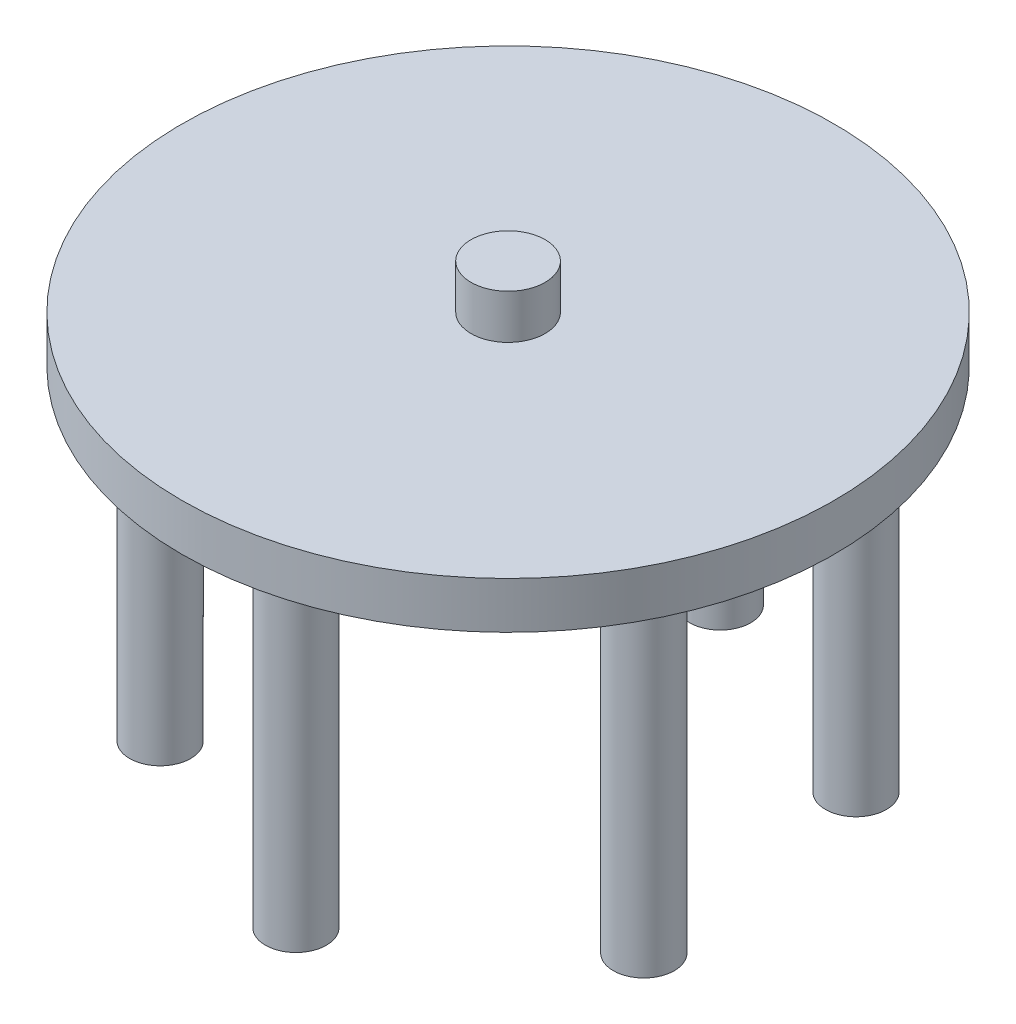
SolidWorks part; units mm, degrees
ref_plane "Front Plane" through (0, 0, 0) normal (0, 0, 1) x (1, 0, 0)
ref_plane "Top Plane" through (0, 0, 0) normal (0, 1, 0) x (1, 0, 0)
ref_plane "Right Plane" through (0, 0, 0) normal (1, 0, 0) x (0, 0, -1)
sketch "Sketch1" plane through (0, 0, 0) normal (0, 1, 0) x (1, 0, 0)
  circle A0 centre (0, 0) radius 27.955
  dimension "D1" = 55.91
extrude "Boss-Extrude1" add sketch "Sketch1" along normal blind 4
sketch "Sketch2" plane through (0, 4, 0) normal (0, 1, 0) x (1, 0, 0)
  circle A0 centre (0, 0) radius 3.175
  dimension "D1" = 6.35
extrude "Boss-Extrude2" add sketch "Sketch2" along normal blind 3.8
sketch "Sketch3" plane through (0, 0, 0) normal (0, -1, 0) x (1, 0, 0)
  circle A0 centre (0, 0) radius 21.2558
  circle A1 centre (2.874, 21.0606) radius 2.6153
  circle A2 centre (19.6761, 8.0413) radius 2.6153
  circle A3 centre (16.802, -13.0193) radius 2.6153
  circle A4 centre (-2.874, -21.0606) radius 2.6153
  circle A5 centre (-19.6761, -8.0413) radius 2.6153
  circle A6 centre (-16.802, 13.0193) radius 2.6153
  point P17 (0, 0)
  dimension "D1" = 6
extrude "Boss-Extrude3" add sketch "Sketch3" along normal blind 29.718 contours A0 A4 | A0 A4 | A0 A3 | A0 A3 | A0 A2 | A0 A2 | A0 A1 | A0 A1 | A0 A6 | A0 A6 | A0 A5 | A0 A5 region at (18.6222, 0, 7.6106) region at (20.6763, 0, 8.4501) region at (17.6561, 0, -13.6811) region at (15.9021, 0, -12.322) region at (2.7201, 0, 19.9327) region at (3.0201, 0, 22.1312) region at (-3.0201, 0, -22.1312) region at (-2.7201, 0, -19.9327) region at (-15.9021, 0, 12.322) region at (-17.6561, 0, 13.6811) region at (-20.6763, 0, -8.4501) region at (-18.6222, 0, -7.6106)
